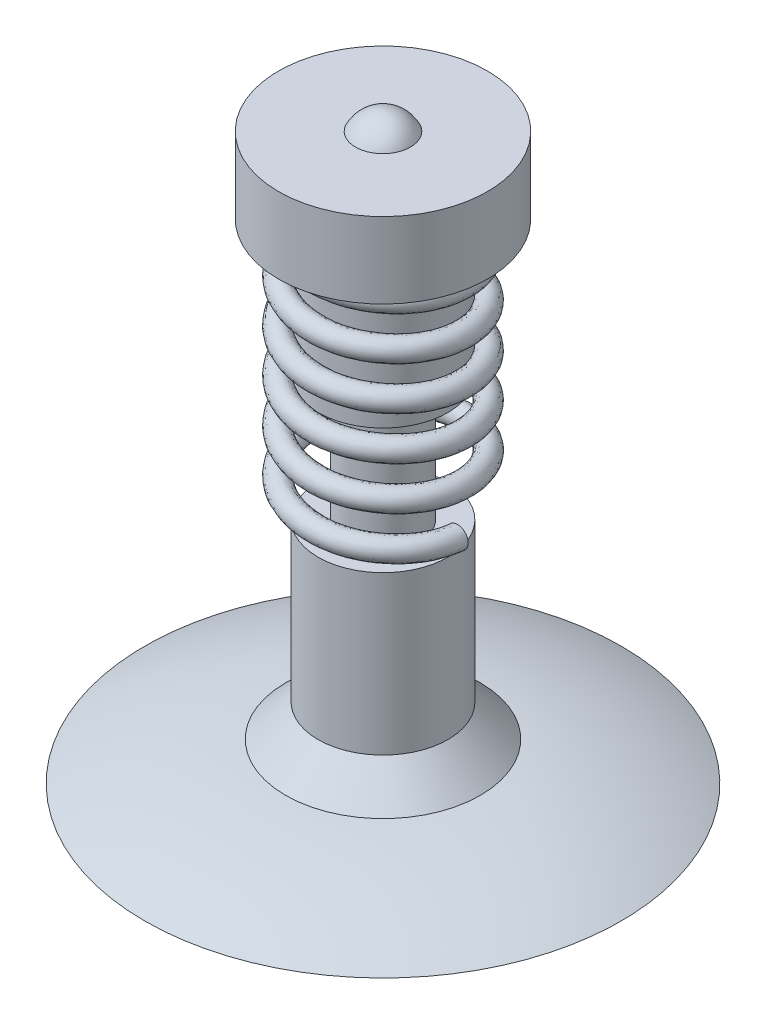
SolidWorks part; units mm, degrees
ref_plane "Front Plane" through (0, 0, 0) normal (0, 0, 1) x (1, 0, 0)
ref_plane "Top Plane" through (0, 0, 0) normal (0, 1, 0) x (1, 0, 0)
ref_plane "Right Plane" through (0, 0, 0) normal (1, 0, 0) x (0, 0, -1)
sketch "Sketch2" plane through (0, 0, 0) normal (0, 0, 1) x (1, 0, 0)
  line L0 (0, 2.69) -> (0, 0)
  line L1 (0, 0) -> (1.1, 0)
  line L2 (0.45, 0.1779) -> (0.3, 0.3258)
  line L3 (0.3, 0.3258) -> (0.3, 1.0555)
  line L4 (0.3, 1.0555) -> (0.172, 1.0555)
  line L5 (0.172, 1.0555) -> (0.172, 1.548)
  line L6 (0.172, 1.548) -> (0.3, 1.634)
  line L7 (0.3, 1.634) -> (0.3, 2.259)
  line L8 (0.3, 2.259) -> (0.4826, 2.259)
  line L9 (0.4826, 2.259) -> (0.4826, 2.609)
  line L10 (0.4826, 2.609) -> (0.1268, 2.609)
  arc A0 (1.1, 0) -> (0.45, 0.1779) centre (0.3, -1.647) ccw
  arc A1 (0.1268, 2.609) -> (0, 2.69) centre (-0.0034, 2.5449) ccw
  point P16 (0.7031, 1.6551)
  point P17 (0.8569, 1.8672)
  point P18 (0.7031, 0.1175)
  point P19 (0.4766, 0.1636)
  point P20 (0.1268, 2.609)
  point P21 (0.3, 0.3258)
  point P22 (0.45, 0.1779)
  dimension "D1" = 2.69
  dimension "D2" = 1.1
  dimension "D3" = 0.35
  dimension "D4" = 0.625
  dimension "D5" = 0.172
  dimension "D6" = 0.3
  dimension "D7" = 0.3
revolve "Revolve1" add sketch "Sketch2" angle 360 about L0
sketch "Sketch3" plane through (0, 2.259, 0) normal (0, -1, 0) x (1, 0, 0)
  circle A0 centre (0, 0) radius 0.344
  dimension "D1" = 0.688
curve "Helix/Spiral1" pitch 0.2 height 1.1 turns 5.5
sketch "Sketch4" plane through (0, 0, 0) normal (0, 0, 1) x (1, 0, 0)
  circle A0 centre (0.344, 2.159) radius 0.0495
  point P2 (0, 0)
  point P3 (0, 0)
sweep "Sweep1" add profiles "Sketch4" path "Helix/Spiral1"
